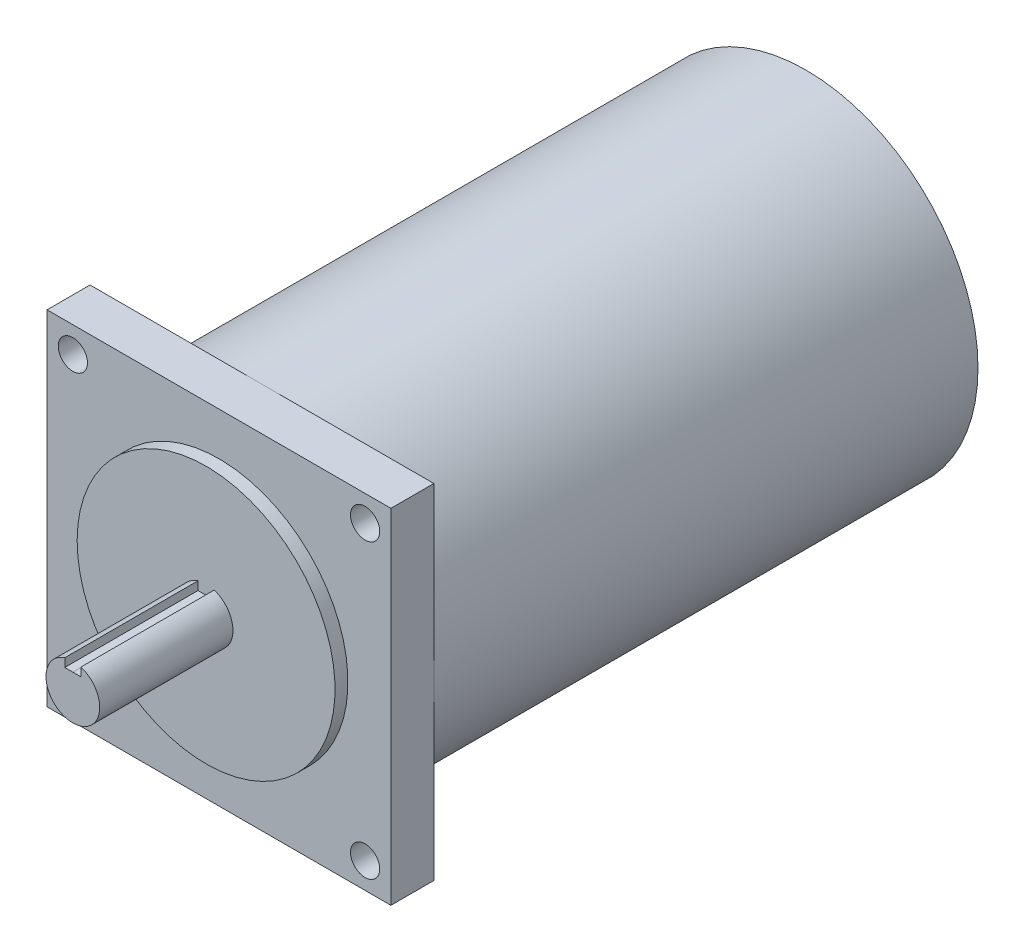
SolidWorks part; units mm, degrees
ref_plane "Front Plane" through (0, 0, 0) normal (0, 0, 1) x (1, 0, 0)
ref_plane "Top Plane" through (0, 0, 0) normal (0, 1, 0) x (1, 0, 0)
ref_plane "Right Plane" through (0, 0, 0) normal (1, 0, 0) x (0, 0, -1)
sketch "Sketch1" plane through (0, 0, 0) normal (0, 0, 1) x (1, 0, 0)
  line L1 (-50.8, 50.8) -> (50.8, 50.8)
  line L2 (-50.8, 50.8) -> (-50.8, -50.8)
  line L3 (-50.8, -50.8) -> (50.8, -50.8)
  line L4 (50.8, 50.8) -> (50.8, -50.8)
  line L5 (-50.8, 50.8) -> (50.8, -50.8) construction
  line L6 (-50.8, -50.8) -> (50.8, 50.8) construction
  circle A0 centre (-43.18, -43.18) radius 4.318
  circle A1 centre (43.18, -43.18) radius 4.318
  circle A2 centre (43.18, 43.18) radius 4.318
  circle A3 centre (-43.18, 43.18) radius 4.318
  point P0 (0, 0)
  dimension "D4" = 8.636
  dimension "D5" = 8.636
  dimension "D6" = 8.636
  dimension "D7" = 8.636
  dimension "D1" = 101.6
  dimension "D2" = 101.6
  dimension "D3" = 86.36
extrude "Boss-Extrude1" add sketch "Sketch1" along normal blind 12.7
sketch "Sketch2" plane through (0, 0, 12.7) normal (0, 0, 1) x (1, 0, 0)
  circle A0 centre (0, 0) radius 38.1
  dimension "D1" = 76.2
extrude "Boss-Extrude2" add sketch "Sketch2" along normal blind 3.81
sketch "Sketch4" plane through (0, 0, 16.51) normal (0, 0, 1) x (1, 0, 0)
  circle A0 centre (0, 0) radius 7.9375
  dimension "D1" = 15.875
extrude "Boss-Extrude4" add sketch "Sketch4" along normal blind 39.37
sketch "Sketch5" plane through (0, 0, 55.88) normal (0, 0, 1) x (1, 0, 0)
  line L1 (0, 5.0638) -> (-2.3876, 5.0638)
  line L2 (-2.3876, 5.0638) -> (-2.3876, 7.5699)
  line L3 (0, 5.0638) -> (2.3876, 5.0638)
  line L4 (2.3876, 5.0638) -> (2.3876, 7.5699)
  circle A0 centre (0, 0) radius 7.9375 construction
  dimension "D1" = 2.5061
  dimension "D2" = 2.3876
  dimension "D3" = 2.3876
  dimension "D4" = 2.5061
extrude "Cut-Extrude1" cut sketch "Sketch5" against normal blind 39.37 and the other way through all
sketch "Sketch6" plane through (0, 0, 0) normal (0, 0, -1) x (-1, 0, 0)
  circle A0 centre (0, 0) radius 50.8
  dimension "D1" = 101.6
extrude "Boss-Extrude5" add sketch "Sketch6" along normal blind 160.782
sketch "Sketch7" plane through (0, 0, -160.782) normal (0, 0, -1) x (-1, 0, 0)
  circle A0 centre (0, 0) radius 38.1
  dimension "D1" = 76.2
extrude "Boss-Extrude6" add sketch "Sketch7" along normal blind 3.81
sketch "Sketch8" plane through (0, 0, -164.592) normal (0, 0, -1) x (-1, 0, 0)
  circle A0 centre (0, 0) radius 6.35
  dimension "D1" = 12.7
extrude "Boss-Extrude7" add sketch "Sketch8" along normal blind 17.78
